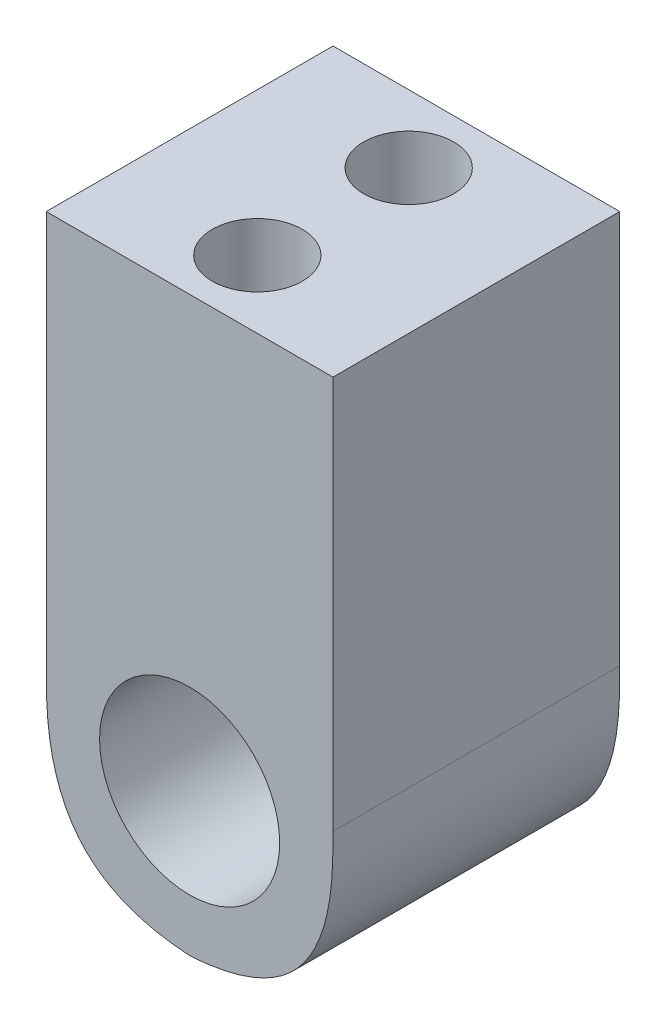
SolidWorks part; units mm, degrees
ref_plane "Front Plane" through (0, 0, 0) normal (0, 0, 1) x (1, 0, 0)
ref_plane "Top Plane" through (0, 0, 0) normal (0, 1, 0) x (1, 0, 0)
ref_plane "Right Plane" through (0, 0, 0) normal (1, 0, 0) x (0, 0, -1)
sketch "Sketch1" plane through (0, 0, 0) normal (0, 0, 1) x (1, 0, 0)
  line L1 (-6.35, 6.35) -> (6.35, 6.35)
  line L2 (-6.35, 6.35) -> (-6.35, -6.35)
  line L3 (-6.35, -6.35) -> (6.35, -6.35)
  line L4 (6.35, 6.35) -> (6.35, -6.35)
  line L5 (-6.35, 6.35) -> (6.35, -6.35) construction
  line L6 (-6.35, -6.35) -> (6.35, 6.35) construction
  line L7 (-6.35, 6.35) -> (6.35, 6.35)
  line L8 (-6.35, 6.35) -> (-6.35, 19.05)
  line L9 (-6.35, 19.05) -> (6.35, 19.05)
  line L10 (6.35, 6.35) -> (6.35, 19.05)
  circle A0 centre (0, 0) radius 3.9878
  point P0 (0, 0)
  dimension "D2" = 7.9756
  dimension "D1" = 12.7
  dimension "D3" = 12.7
  dimension "D4" = 12.7
extrude "Boss-Extrude1" add sketch "Sketch1" against normal blind 12.7 contours L1 L10 L9 L8 | L4 L1 L2 L3 A0 | A0 region at (0, 12.7, 0) region at (0, 6.1704, 0) region at (0, 0, 0)
fillet "Fillet1" radius 7.9756 2 edges at (-6.35, -6.35, -6.35) (6.35, -6.35, -6.35) curvature continuous yes
sketch "Sketch3" plane through (0, 19.05, 0) normal (0, 1, 0) x (1, 0, 0)
  line L0 (0, 9.7028) -> (0, 6.35) construction
  line L1 (0, 6.35) -> (0, 2.9972) construction
  line L4 (-6.35, 0) -> (6.35, 0)
  line L5 (6.35, 0) -> (6.35, 12.7)
  line L6 (6.35, 12.7) -> (-6.35, 12.7)
  line L7 (-6.35, 12.7) -> (-6.35, 0)
  line L8 (-6.35, 0) -> (6.35, 0)
  line L9 (6.35, 0) -> (6.35, 12.7)
  line L10 (6.35, 12.7) -> (-6.35, 12.7)
  line L11 (-6.35, 12.7) -> (-6.35, 0)
  circle A0 centre (0, 9.7028) radius 1.9939
  circle A1 centre (0, 2.9972) radius 1.9939
  point P2 (0, 0)
  point P4 (0, 12.7)
  point P7 (6.35, 6.35)
  dimension "D3" = 3.9878
  dimension "D4" = 3.9878
  dimension "D2" = 6.7056
  dimension "D1" = 0
extrude "Cut-Extrude2" cut sketch "Sketch3" against normal blind 6.35 contours A0 | A0 | A0 | A0 | A1 | A1 | A1 | A1 region at (0, 19.05, -9.7028) region at (0, 19.05, -2.9972)
extrude "Cut-Extrude3" cut sketch "Sketch1<3>" against normal through all contours A0
sketch "Sketch1<3>" plane through (0, 0, 0) normal (0, 0, 1) x (1, 0, 0) same geometry as "Sketch1"
